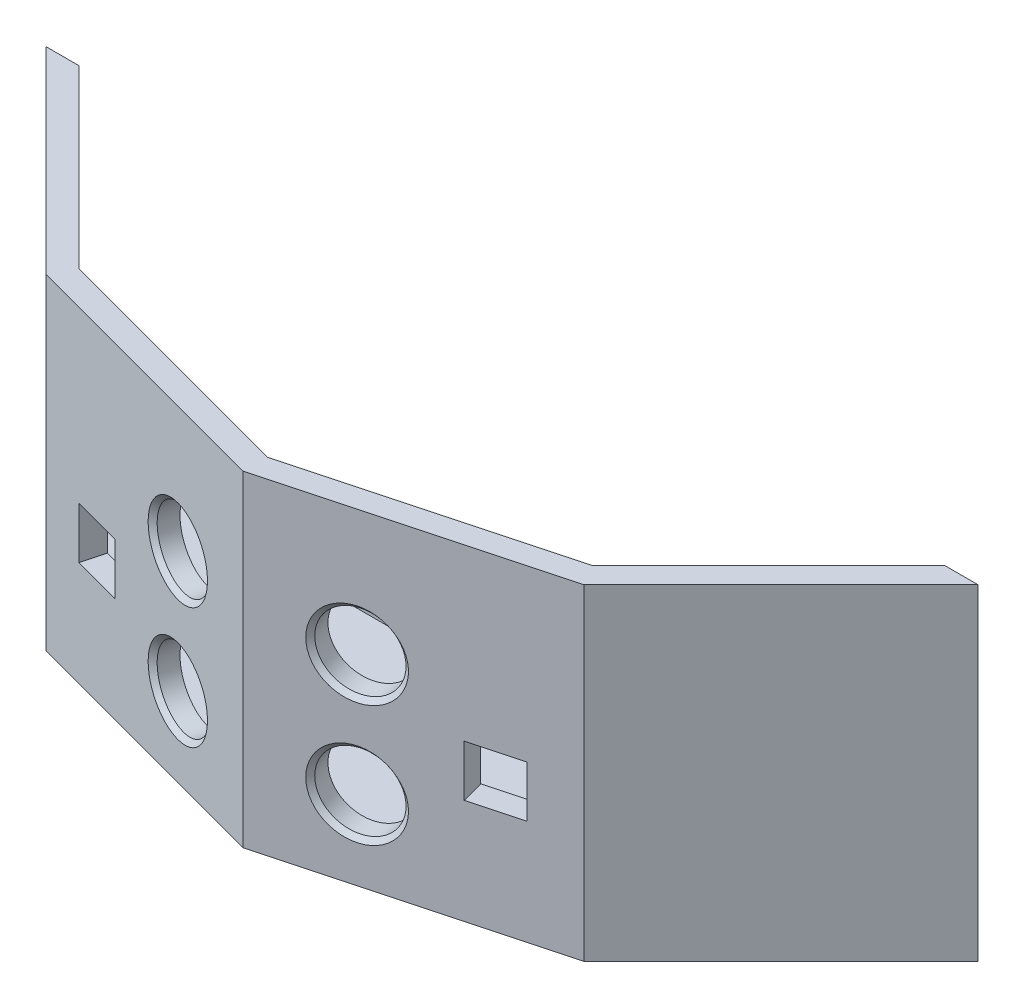
SolidWorks part; units mm, degrees
ref_plane "Front Plane" through (0, 0, 0) normal (0, 0, 1) x (1, 0, 0)
ref_plane "Top Plane" through (0, 0, 0) normal (0, 1, 0) x (1, 0, 0)
ref_plane "Right Plane" through (0, 0, 0) normal (1, 0, 0) x (0, 0, -1)
sketch "Sketch1" plane through (0, 0, 0) normal (0, 1, 0) x (1, 0, 0)
  line L0 (57.735, -100) -> (100, -57.735)
  line L14 (-100, -57.735) -> (-57.735, -100)
  line L15 (-57.735, -100) -> (0, -115.4701)
  line L16 (0, -115.4701) -> (57.735, -100)
  line L18 (-100, -57.735) -> (100, -57.735)
  line L23 (107.735, -28.8675) -> (115.4701, 0) [skipped]
  line L24 (-115.4701, 0) -> (-107.735, -28.8675) [skipped]
  line L25 (-100, 57.735) -> (-107.735, 28.8675) [skipped]
  line L26 (100, 57.735) -> (78.8675, 78.8675) [skipped]
  line L27 (115.4701, 0) -> (100, 57.735) [skipped]
  line L28 (28.8675, 107.735) -> (0, 115.4701) [skipped]
  line L29 (0, 115.4701) -> (-28.8675, 107.735) [skipped]
  line L30 (-57.735, 100) -> (-78.8675, 78.8675) [skipped]
  arc A1 (-95.4297, -57.735) -> (95.4297, -57.735) centre (0, 0) ccw construction
  dimension "D1" = 200
  dimension "D2" = 57.735
extrude "Boss-Extrude1" add sketch "Sketch1" along normal blind 70
sketch "Sketch4" plane through (0, 70, 0) normal (0, 1, 0) x (1, 0, 0)
  line L1 (110.2937, 0) -> (95.5171, 55.1468)
  line L2 (95.5171, 55.1468) -> (55.1468, 95.5171)
  line L3 (55.1468, 95.5171) -> (0, 110.2937)
  line L4 (0, 110.2937) -> (-55.1468, 95.5171)
  line L5 (-55.1468, 95.5171) -> (-95.5171, 55.1468)
  line L6 (-95.5171, 55.1468) -> (-110.2937, 0)
  line L7 (-110.2937, 0) -> (-95.5171, -55.1468)
  line L8 (-95.5171, -55.1468) -> (-55.1468, -95.5171)
  line L9 (-55.1468, -95.5171) -> (0, -110.2937)
  line L10 (0, -110.2937) -> (55.1468, -95.5171)
  line L11 (55.1468, -95.5171) -> (95.5171, -55.1468)
  line L12 (95.5171, -55.1468) -> (110.2937, 0)
  line L13 (-57.735, -100) -> (0, -115.4701) construction
  circle A0 centre (0, 0) radius 106.5355 construction
  dimension "D1" = 5
extrude "Cut-Extrude1" cut sketch "Sketch4" against normal blind 65
sketch "Sketch5" plane through (-28.8675, 0, 107.735) normal (-0.2588, 0, 0.9659) x (0.9659, 0, 0.2588)
  line L0 (-29.8858, 0) -> (29.8858, 0) construction
  line L1 (-10.0008, 51) -> (9.9992, 51) construction
  line L2 (-10.0008, 51) -> (-10.0008, 8) construction
  line L3 (-10.0008, 8) -> (9.9992, 8) construction
  line L4 (9.9992, 51) -> (9.9992, 8) construction
  line L5 (-29.8858, 70) -> (-29.8858, 0) construction
  circle A0 centre (10.1142, 43) radius 8
  circle A1 centre (10.1142, 17) radius 8
  dimension "D5" = 16
  dimension "D6" = 16
  dimension "D7" = 9
  dimension "D1" = 8
  dimension "D2" = 20
  dimension "D3" = 43
  dimension "D4" = 40
  dimension "D8" = 26
extrude "Cut-Extrude2" cut sketch "Sketch5" against normal blind 10
sketch "Sketch6" plane through (28.8675, 0, 107.735) normal (0.2588, 0, 0.9659) x (0.9659, 0, -0.2588)
  line L1 (-19.8858, 51) -> (0.1142, 51) construction
  line L2 (-19.8858, 51) -> (-19.8858, 8) construction
  line L3 (-19.8858, 8) -> (0.1142, 8) construction
  line L4 (0.1142, 51) -> (0.1142, 8) construction
  line L6 (-29.8858, 70) -> (-29.8858, 0) construction
  line L7 (-29.8858, 0) -> (29.8858, 0) construction
  circle A0 centre (-9.8858, 17) radius 8
  circle A1 centre (-9.8858, 43) radius 8
  point P4 (5.1142, 27.5)
  dimension "D5" = 16
  dimension "D6" = 16
  dimension "D2" = 43
  dimension "D3" = 20
  dimension "D4" = 8
  dimension "D7" = 9
  dimension "D8" = 26
  dimension "D9" = 10
  dimension "D10" = 10
  dimension "D11" = 20
extrude "Cut-Extrude3" cut sketch "Sketch6" against normal blind 10
chamfer "Chamfer2" distance 1 angle 45 4 edges at (27.0459, 17, 108.2231) (27.0459, 43, 108.2231) (-11.3706, 17, 112.4233) (-11.3706, 43, 112.4233)
sketch "Sketch7" plane through (-28.8675, 0, 107.735) normal (-0.2588, 0, 0.9659) x (0.9659, 0, 0.2588)
  line L0 (-29.8858, 0) -> (29.8858, 0) construction
  line L1 (-19.8858, 33.5) -> (-8.8858, 33.5)
  line L2 (-19.8858, 33.5) -> (-19.8858, 22.5)
  line L3 (-19.8858, 22.5) -> (-8.8858, 22.5)
  line L4 (-8.8858, 33.5) -> (-8.8858, 22.5)
  line L5 (-19.8858, 33.5) -> (-8.8858, 22.5) construction
  line L6 (-19.8858, 22.5) -> (-8.8858, 33.5) construction
  line L7 (-29.8858, 70) -> (-29.8858, 0) construction
  point P4 (-14.3858, 28)
  dimension "D1" = 11
  dimension "D2" = 28
  dimension "D3" = 10
extrude "Cut-Extrude4" cut sketch "Sketch7" against normal blind 10
sketch "Sketch8" plane through (28.8675, 0, 107.735) normal (0.2588, 0, 0.9659) x (0.9659, 0, -0.2588)
  line L0 (29.8858, 70) -> (29.8858, 0) construction
  line L1 (8.8858, 33.5) -> (19.8858, 33.5)
  line L2 (8.8858, 33.5) -> (8.8858, 22.5)
  line L3 (8.8858, 22.5) -> (19.8858, 22.5)
  line L4 (19.8858, 33.5) -> (19.8858, 22.5)
  line L5 (8.8858, 33.5) -> (19.8858, 22.5) construction
  line L6 (8.8858, 22.5) -> (19.8858, 33.5) construction
  line L7 (-29.8858, 0) -> (29.8858, 0) construction
  point P4 (14.3858, 28)
  dimension "D1" = 11
  dimension "D2" = 11
  dimension "D3" = 10
  dimension "D4" = 28
extrude "Cut-Extrude5" cut sketch "Sketch8" against normal blind 10
sketch "Sketch9" plane through (0, 0, 57.735) normal (0, 0, -1) x (-1, 0, 0)
  line L0 (0, 5) -> (-55.1468, 5) construction
  line L1 (-33, 5) -> (-20, 5)
  line L2 (-33, 5) -> (-33, 15)
  line L3 (-33, 15) -> (-20, 15)
  line L4 (-20, 5) -> (-20, 15)
  line L5 (-33, 5) -> (-20, 15) construction
  line L6 (-33, 15) -> (-20, 5) construction
  line L7 (55.1468, 5) -> (0, 5) construction
  line L8 (20, 5) -> (33, 5)
  line L9 (20, 5) -> (20, 15)
  line L10 (20, 15) -> (33, 15)
  line L11 (33, 5) -> (33, 15)
  line L12 (20, 5) -> (33, 15) construction
  line L13 (20, 15) -> (33, 5) construction
  point P4 (-26.5, 10)
  point P11 (26.5, 10)
  dimension "D1" = 13
  dimension "D2" = 13
  dimension "D3" = 20
  dimension "D4" = 20
  dimension "D5" = 10
  dimension "D6" = 10
extrude "Boss-Extrude2" add sketch "Sketch9" against normal blind 6
sketch "Sketch10" plane through (0, 0, 57.735) normal (0, 0, -1) x (-1, 0, 0)
  line L0 (0, 5) -> (-55.1468, 5) construction
  line L1 (55.1468, 5) -> (0, 5) construction
  circle A0 centre (-26.5, 11) radius 2
  circle A1 centre (26.5, 11) radius 2
  dimension "D1" = 4
  dimension "D2" = 4
  dimension "D3" = 6
  dimension "D4" = 6
  dimension "D5" = 53
  dimension "D6" = 26.5
extrude "Cut-Extrude6" cut sketch "Sketch10" against normal blind 10
fillet "Fillet1" radius 5 8 edges at (-33, 5, 60.735) (-33, 15, 60.735) (-20, 15, 60.735) (-20, 5, 60.735) (20, 5, 60.735) (20, 15, 60.735) (33, 15, 60.735) (33, 5, 60.735)
